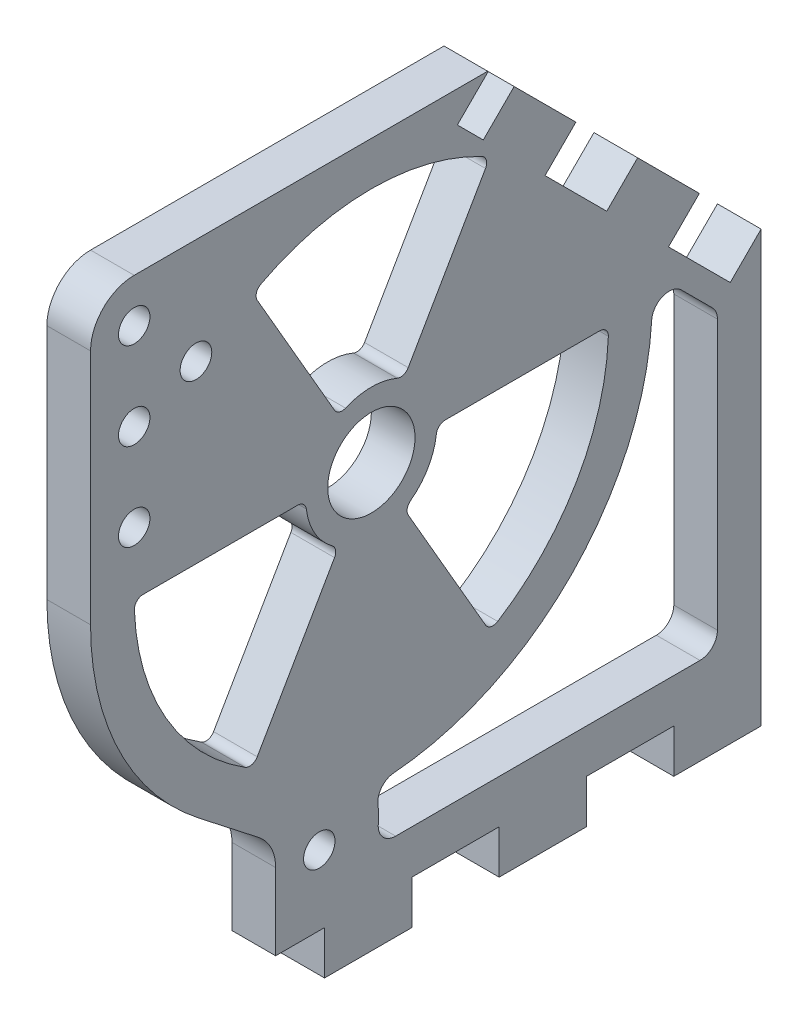
SolidWorks part; units mm, degrees
material "Custom Plastic"
ref_plane "Front Plane" through (0, 0, 0) normal (0, 0, 1) x (1, 0, 0)
ref_plane "Top Plane" through (0, 0, 0) normal (0, 1, 0) x (1, 0, 0)
ref_plane "Right Plane" through (0, 0, 0) normal (1, 0, 0) x (0, 0, -1)
sketch "Sketch2" plane through (0, 0, 0) normal (1, 0, 0) x (0, 0, -1)
  line L0 (-28.956, 10.16) -> (-35.306, 10.16) construction
  line L1 (-35.306, 0) -> (-35.306, 14.2168)
  line L2 (-35.306, 14.2168) -> (-46.5136, 22.9635)
  line L4 (-55.88, 89.662) -> (-55.88, 76.962) construction
  line L5 (-35.306, 0) -> (35.306, 0)
  line L6 (-62.23, 96.012) -> (-62.23, 55.1649)
  line L7 (-55.88, 76.962) -> (-55.88, 64.262) construction
  line L10 (-62.23, 96.012) -> (-4.4635, 96.012)
  line L11 (-55.88, 89.662) -> (-55.88, 96.012) construction
  line L12 (-55.88, 89.662) -> (-62.23, 89.662) construction
  line L24 (-4.4635, 96.012) -> (35.306, 56.2425)
  line L25 (35.306, 56.2425) -> (35.306, 0)
  circle A0 centre (-55.88, 89.662) radius 2.286
  circle A1 centre (-28.956, 10.16) radius 2.286
  circle A2 centre (-55.88, 89.662) radius 87.503 construction
  circle A3 centre (-28.956, 10.16) radius 126.6734 construction
  circle A4 centre (-21.3829, 55.1649) radius 40.8471 construction
  circle A5 centre (-55.88, 76.962) radius 2.286
  circle A6 centre (-55.88, 64.262) radius 2.286
  arc A7 (-62.23, 55.1649) -> (-46.5136, 22.9635) centre (-21.3829, 55.1649) ccw
  point P0 (0, 0)
  point P1 (-55.88, 89.662)
  point P3 (-28.956, 10.16)
  point P34 (0, 0)
  dimension "D4" = 45
  dimension "D16" = 253.3467
  dimension "D19" = 175.006
  dimension "D2" = 4.572
  dimension "D3" = 6.35
  dimension "D5" = 12.7
  dimension "D14" = 28.956
  dimension "D15" = 10.16
  dimension "D17" = 89.662
  dimension "D18" = 55.88
extrude "Main" add sketch "Sketch2" along normal blind 6.35 contours A1 A0 region at (0, 47.4384, 13.2547)
sketch "Sketch3" plane through (6.35, 0, 0) normal (1, 0, 0) x (0, 0, -1)
  line L0 (-2.794, -6.35) -> (9.906, -6.35)
  line L1 (-28.194, 0) -> (-15.494, 0)
  line L2 (-28.194, 0) -> (-28.194, -6.35)
  line L3 (-28.194, -6.35) -> (-15.494, -6.35)
  line L4 (-15.494, 0) -> (-15.494, -6.35)
  line L5 (9.906, 0) -> (9.906, -6.35)
  line L6 (-2.794, 0) -> (9.906, 0)
  line L7 (-2.794, 0) -> (-2.794, -6.35)
  line L8 (22.606, -6.35) -> (35.306, -6.35)
  line L9 (35.306, 0) -> (35.306, -6.35)
  line L10 (22.606, 0) -> (35.306, 0)
  line L11 (22.606, 0) -> (22.606, -6.35)
  line L12 (-28.194, -6.35) -> (-2.794, -6.35) construction
  line L13 (-35.306, 0) -> (35.306, 0) construction
  line L16 (35.306, 56.2425) -> (35.306, 0) construction
  dimension "D1" = 12.7
  dimension "D2" = 6.35
  dimension "D4" = 25.4
  dimension "D3" = 3
extrude "plate mount 1" add sketch "Sketch3" against normal through all
sketch "Sketch4" plane through (0, 0, 0) normal (-1, 0, 0) x (0, 0, 1)
  line L0 (4.3867, 95.9353) -> (0.615, 92.1636) construction
  line L1 (0.615, 92.1636) -> (5.1052, 87.6734) construction
  line L2 (5.1052, 87.6734) -> (8.8769, 91.4451) construction
  line L3 (8.8769, 91.4451) -> (4.3867, 95.9353) construction
  line L4 (-12.8554, 69.7129) -> (-3.8751, 78.6932) construction
  line L5 (-3.8751, 78.6932) -> (-8.3652, 83.1833) construction
  line L6 (-8.3652, 83.1833) -> (-17.3455, 74.203) construction
  line L7 (-17.3455, 74.203) -> (-12.8554, 69.7129) construction
  line L8 (-30.8159, 51.7524) -> (-21.8356, 60.7327) construction
  line L9 (-21.8356, 60.7327) -> (-26.3257, 65.2228) construction
  line L10 (-26.3257, 65.2228) -> (-35.306, 56.2425) construction
  line L11 (-35.306, 56.2425) -> (-30.8159, 51.7524) construction
  line L12 (4.3867, 95.9353) -> (0.615, 92.1636)
  line L13 (0.615, 92.1636) -> (5.1052, 87.6734)
  line L14 (5.1052, 87.6734) -> (8.8769, 91.4451)
  line L15 (8.8769, 91.4451) -> (4.3867, 95.9353)
  line L16 (-12.8554, 69.7129) -> (-3.8751, 78.6932)
  line L17 (-3.8751, 78.6932) -> (-8.3652, 83.1833)
  line L18 (-8.3652, 83.1833) -> (-17.3455, 74.203)
  line L19 (-17.3455, 74.203) -> (-12.8554, 69.7129)
  line L20 (-30.8159, 51.7524) -> (-21.8356, 60.7327)
  line L21 (-21.8356, 60.7327) -> (-26.3257, 65.2228)
  line L22 (-26.3257, 65.2228) -> (-35.306, 56.2425)
  line L23 (-35.306, 56.2425) -> (-30.8159, 51.7524)
extrude "plate mount 2" cut sketch "Sketch4" against normal through all
sketch "Sketch5" plane through (6.35, 0, 0) normal (1, 0, 0) x (0, 0, -1)
  line L0 (-55.88, 89.662) -> (-46.8997, 80.6817) construction
  line L1 (-46.8997, 80.6817) -> (-62.23, 80.6817) construction
  line L2 (-62.23, 96.012) -> (-62.23, 55.1649) construction
  circle A0 centre (-46.8997, 80.6817) radius 2.3026
  arc A1 (-63.232, 82.31) -> (-48.528, 82.31) centre (-55.88, 89.662) ccw construction
  arc A39 (-66.4885, 79.0535) -> (-45.2715, 79.0535) centre (-55.88, 89.662) ccw construction
  dimension "D1" = 45
extrude "pot mount hole" cut sketch "Sketch5" against normal through all
sketch "Sketch6" plane through (6.35, 0, 0) normal (1, 0, 0) x (0, 0, -1)
  line L1 (-4.1343, 85.0403) -> (-21.3829, 55.1649) construction
  line L2 (-21.3829, 55.1649) -> (-38.6314, 25.2895) construction
  line L3 (-55.88, 55.1649) -> (-21.3829, 55.1649) construction
  line L4 (-21.3829, 55.1649) -> (13.1142, 55.1649) construction
  line L5 (-4.1343, 25.2895) -> (-21.3829, 55.1649) construction
  line L6 (-21.3829, 55.1649) -> (-38.6314, 85.0403) construction
  line L7 (-55.88, 55.1649) -> (-38.6314, 85.0403) construction
  line L8 (-38.6314, 85.0403) -> (-4.1343, 85.0403) construction
  line L9 (-4.1343, 85.0403) -> (13.1142, 55.1649) construction
  line L10 (13.1142, 55.1649) -> (-4.1343, 25.2895) construction
  line L11 (-4.1343, 25.2895) -> (-38.6314, 25.2895) construction
  line L12 (-38.6314, 25.2895) -> (-55.88, 55.1649) construction
  line L13 (-30.9079, 55.1649) -> (-55.88, 55.1649)
  line L14 (-26.1454, 46.916) -> (-38.6314, 25.2895)
  line L15 (-16.6204, 46.916) -> (-4.1343, 25.2895)
  line L16 (-11.8579, 55.1649) -> (13.1142, 55.1649)
  line L17 (-16.6204, 63.4138) -> (-4.1343, 85.0403)
  line L18 (-26.1454, 63.4138) -> (-38.6314, 85.0403)
  circle A0 centre (-21.3829, 55.1649) radius 34.4971 construction
  arc A1 (-62.23, 55.1649) -> (-46.5136, 22.9635) centre (-21.3829, 55.1649) ccw construction
  arc A2 (-62.23, 55.1649) -> (-46.5136, 22.9635) centre (-21.3829, 55.1649) ccw construction
  circle A3 centre (-21.3829, 55.1649) radius 6.35
  arc A4 (-26.1454, 63.4138) -> (-16.6204, 63.4138) centre (-21.3829, 55.1649) cw
  arc A5 (-11.8579, 55.1649) -> (-16.6204, 46.916) centre (-21.3829, 55.1649) cw
  arc A6 (-30.9079, 55.1649) -> (-26.1454, 46.916) centre (-21.3829, 55.1649) ccw
  arc A7 (-55.88, 55.1649) -> (-38.6314, 25.2895) centre (-21.3829, 55.1649) ccw
  arc A8 (13.1142, 55.1649) -> (-4.1343, 25.2895) centre (-21.3829, 55.1649) cw
  arc A9 (-38.6314, 85.0403) -> (-4.1343, 85.0403) centre (-21.3829, 55.1649) cw
  dimension "D1" = 6.35
  dimension "D2" = 3.175
  dimension "D3" = 12.7
extrude "radioactive" cut sketch "Sketch6" against normal through all contours L13 A7 L14 A6 | A8 L16 A5 L15 | A9 L18 A4 L17 | A3 region at (6.35, 43.5281, 41.5384) region at (6.35, 43.5281, 1.2274) region at (6.35, 78.4385, 21.3829)
fillet "radioactive  fillet" radius 1.27 12 edges at (3.175, 63.4138, 26.1454) (3.175, 63.4138, 16.6204) (3.175, 55.1649, 30.9079) (3.175, 46.916, 26.1454) (3.175, 46.916, 16.6204) (3.175, 55.1649, 11.8579) (3.175, 25.2895, 38.6314) (3.175, 25.2895, 4.1343) (3.175, 85.0403, 4.1343) (3.175, 55.1649, -13.1142) (3.175, 85.0403, 38.6314) (3.175, 55.1649, 55.88)
sketch "Sketch7" plane through (6.35, 0, 0) normal (1, 0, 0) x (0, 0, -1)
  line L0 (-28.956, 15.026) -> (-28.956, 6.35) construction
  line L1 (-28.956, 6.35) -> (28.956, 6.35) construction
  line L2 (28.956, 6.35) -> (28.956, 49.1221) construction
  line L3 (28.956, 49.1221) -> (19.3045, 58.7737) construction
  line L4 (17.3455, 74.203) -> (26.3257, 65.2228) construction
  line L5 (35.306, 56.2425) -> (35.306, -6.35) construction
  line L6 (9.906, 0) -> (22.606, 0) construction
  line L7 (-35.306, 0) -> (-35.306, 14.2168) construction
  line L8 (-15.494, 0) -> (-2.794, 0) construction
  line L9 (30.8159, 51.7524) -> (21.8356, 60.7327) construction
  line L10 (19.3045, 58.7737) -> (28.956, 49.1221)
  line L11 (28.956, 49.1221) -> (28.956, 6.35)
  line L12 (28.956, 6.35) -> (-21.2021, 6.35)
  circle A0 centre (-21.3829, 55.1649) radius 40.8471 construction
  arc A1 (-62.23, 55.1649) -> (-46.5136, 22.9635) centre (-21.3829, 55.1649) ccw construction
  circle A2 centre (-28.956, 10.16) radius 8.636 construction
  circle A4 centre (-28.956, 10.16) radius 2.286 construction
  arc A5 (-21.3829, 14.3178) -> (-21.2021, 6.35) centre (-28.956, 10.16) cw
  arc A6 (-21.3829, 14.3178) -> (19.3045, 58.7737) centre (-21.3829, 55.1649) ccw
  point P21 (26.3257, 56.2425)
  dimension "D5" = 6.35
  dimension "D1" = 6.35
  dimension "D2" = 6.35
  dimension "D3" = 6.35
  dimension "D4" = 3.175
extrude "Cut-Extrude4" cut sketch "Sketch7" against normal through all contours A6 A5 L12 L11 L10 region at (6.35, 22.4334, -12.7277)
fillet "Fillet2" radius 6.35 2 edges at (3.175, 14.2168, 35.306) (3.175, 96.012, 62.23)
fillet "Fillet3" radius 2.54 5 edges at (3.175, 6.35, 21.2021) (3.175, 6.35, -28.956) (3.175, 49.1221, -28.956) (3.175, 58.7737, -19.3045) (3.175, 14.3178, 21.3829)
